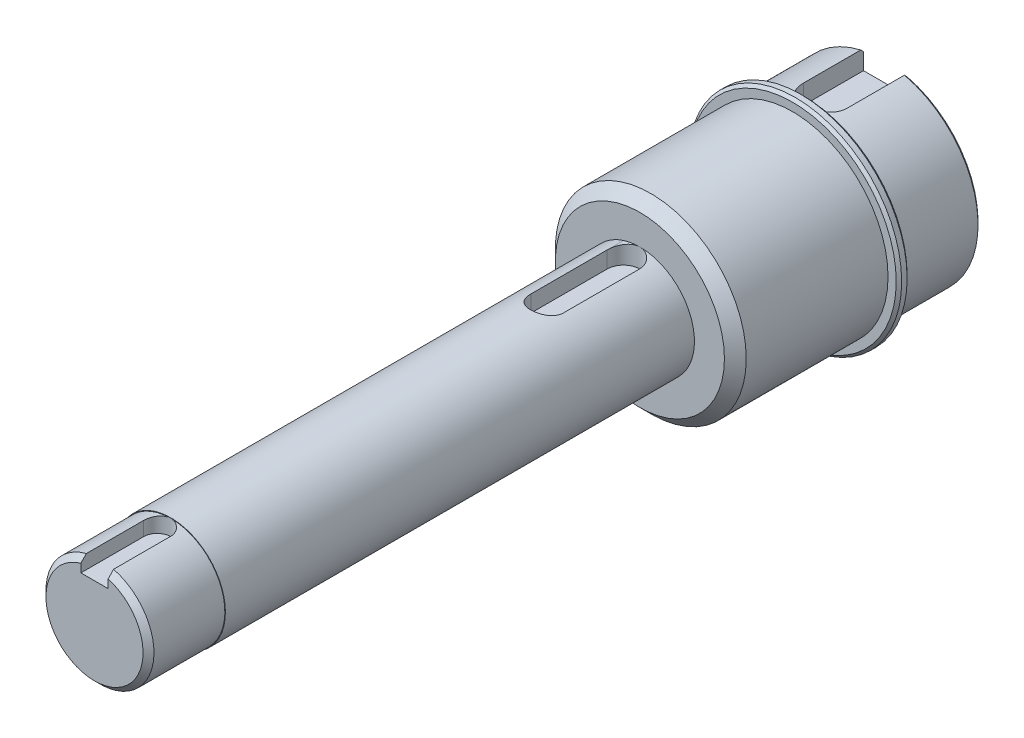
SolidWorks part; units mm, degrees
ref_plane "前视基准面" through (0, 0, 0) normal (0, 0, 1) x (1, 0, 0)
ref_plane "上视基准面" through (0, 0, 0) normal (0, 1, 0) x (1, 0, 0)
ref_plane "右视基准面" through (0, 0, 0) normal (1, 0, 0) x (0, 0, -1)
sketch "草图1" plane through (0, 0, 0) normal (0, 0, 1) x (1, 0, 0)
  circle A0 centre (0, 0) radius 17.5
  dimension "D1" = 35
extrude "拉伸1" add sketch "草图1" along normal blind 15
sketch "草图2" plane through (0, 0, 15) normal (0, 0, 1) x (1, 0, 0)
  circle A0 centre (0, 0) radius 19.5
extrude "拉伸2" add sketch "草图2" along normal blind 2
sketch "草图3" plane through (0, 0, 17) normal (0, 0, 1) x (1, 0, 0)
  circle A0 centre (0, 0) radius 17.5
extrude "拉伸3" add sketch "草图3" along normal blind 28
sketch "草图4" plane through (0, 0, 45) normal (0, 0, 1) x (1, 0, 0)
  circle A0 centre (0, 0) radius 10
extrude "拉伸4" add sketch "草图4" along normal blind 100
chamfer "倒角1" distance 2 angle 45 1 edges at (17.5, 0, 45)
sketch "草图5" plane through (0, 0, 145) normal (0, 0, 1) x (1, 0, 0)
  circle A0 centre (0, 0) radius 10
  circle A1 centre (0, 0) radius 9.9
extrude "切除-拉伸1" cut sketch "草图5" against normal blind 14
chamfer "倒角2" distance 1 angle 45 1 edges at (9.9, 0, 145)
ref_plane "基准面1" through (0, 10, 0) normal (0, 1, 0) x (-1, 0, 0)
sketch "草图6" plane through (0, 10, 0) normal (0, 1, 0) x (-1, 0, 0)
  line L0 (15.5, 45) -> (-15.5, 45) construction
  line L1 (-3, 62) -> (-3, 48)
  line L2 (3, 62) -> (3, 48)
  arc A0 (-3, 48) -> (3, 48) centre (0, 48) ccw
  arc A1 (3, 62) -> (-3, 62) centre (0, 62) ccw
  dimension "D1" = 6
  dimension "D2" = 6
  dimension "D3" = 14
  dimension "D4" = 3
extrude "切除-拉伸2" cut sketch "草图6" against normal blind 3.5
ref_axis "基准轴1" through (0, 0, 43) along (0, 0, -1)
ref_plane "基准面2" through (0, 17.5, 0) normal (0, 1, 0) x (-1, 0, 0)
sketch "草图8" plane through (0, 17.5, 0) normal (0, 1, 0) x (-1, 0, 0)
  line L0 (0, 43) -> (0, 17) construction
  line L1 (-17.5, 15) -> (17.5, 15) construction
  line L2 (-4, 11) -> (-4, 0)
  line L3 (-17.5, 0) -> (17.5, 0) construction
  line L4 (-4, 0) -> (4, 0)
  line L5 (4, 0) -> (4, 11)
  arc A0 (4, 11) -> (-4, 11) centre (0, 11) ccw
  dimension "D1" = 4
  dimension "D2" = 4
extrude "切除-拉伸3" cut sketch "草图8" against normal blind 4
sketch "草图9" plane through (0, 0, 0) normal (0, 0, -1) x (-1, 0, 0)
  circle A0 centre (0, 0) radius 2.5
  dimension "D1" = 5
extrude "切除-拉伸4" cut sketch "草图9" against normal blind 20
chamfer "倒角3" distance 1 angle 45 1 edges at (-2.5, 0, 0)
chamfer "倒角4" distance 0.5 angle 45 1 edges at (0, -17.5, 0)
chamfer "倒角5" distance 0.5 angle 45 2 edges at (19.5, 0, 17) (19.5, 0, 15)
ref_plane "基准面3" through (0, 10, 0) normal (0, 1, 0) x (-1, 0, 0)
sketch "草图10" plane through (0, 10, 0) normal (0, 1, 0) x (-1, 0, 0)
  line L0 (10, 131) -> (-10, 131) construction
  line L1 (-2.5, 133.5) -> (-2.5, 145)
  line L2 (8.9, 145) -> (-8.9, 145) construction
  line L3 (-2.5, 145) -> (2.5, 145)
  line L4 (2.5, 145) -> (2.5, 133.5)
  arc A0 (-2.5, 133.5) -> (2.5, 133.5) centre (0, 133.5) ccw
  dimension "D1" = 5
  dimension "D2" = 2.5
extrude "切除-拉伸5" cut sketch "草图10" against normal blind 3
